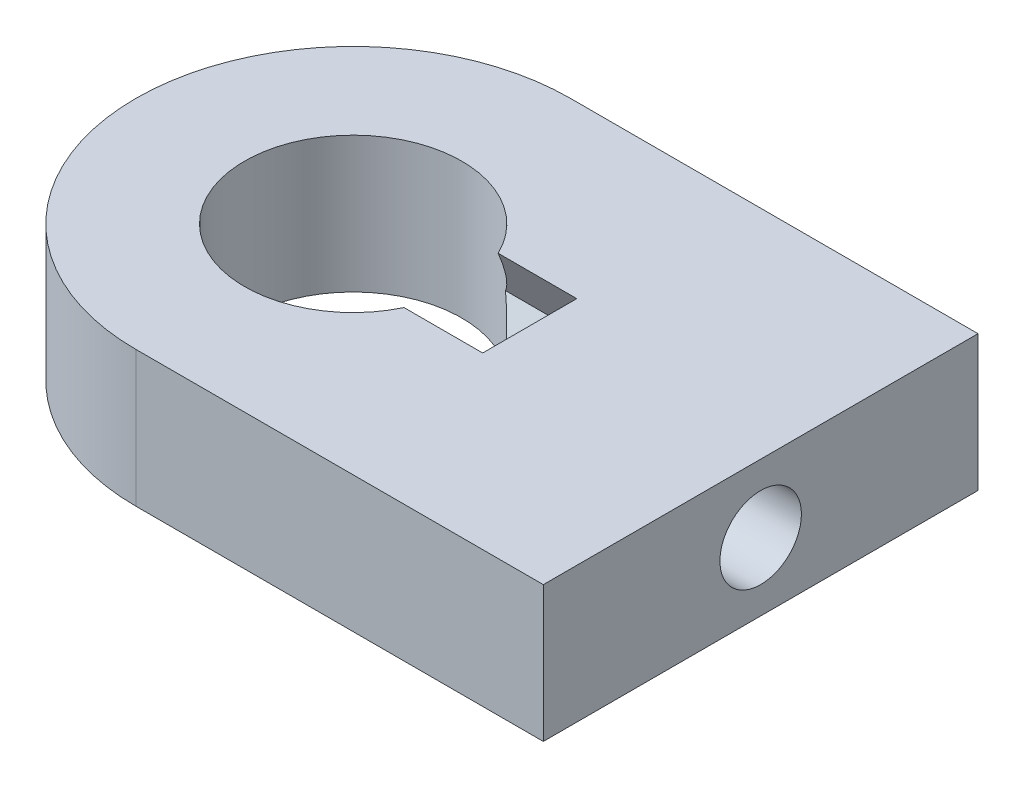
SolidWorks part; units mm, degrees
material "ABS"
ref_plane "Front Plane" through (0, 0, 0) normal (0, 0, 1) x (1, 0, 0)
ref_plane "Top Plane" through (0, 0, 0) normal (0, 1, 0) x (1, 0, 0)
ref_plane "Right Plane" through (0, 0, 0) normal (1, 0, 0) x (0, 0, -1)
sketch "Sketch1" plane through (0, 0, 0) normal (0, 1, 0) x (1, 0, 0)
  line L0 (0, 8) -> (15, 8)
  line L1 (15, 8) -> (15, -8)
  line L2 (15, -8) -> (0, -8)
  circle A0 centre (0, 0) radius 4
  arc A1 (0, -8) -> (0, 8) centre (0, 0) cw
  dimension "D1" = 8
  dimension "D2" = 8
  dimension "D3" = 15
extrude "Boss-Extrude1" add sketch "Sketch1" along normal blind 5
sketch "Sketch2" plane through (15, 0, 0) normal (1, 0, 0) x (0, 0, -1)
  line L0 (0, -3.0185) -> (0, 8.0813) construction
  line L1 (3.1754, 2.5) -> (1.5877, 5.25)
  line L2 (1.5877, 5.25) -> (-1.5877, 5.25)
  line L3 (-1.5877, 5.25) -> (-3.1754, 2.5)
  line L4 (-3.1754, 2.5) -> (-1.5877, -0.25)
  line L5 (-1.5877, -0.25) -> (1.5877, -0.25)
  line L6 (1.5877, -0.25) -> (3.1754, 2.5)
  line L7 (-8, 2.5) -> (8, 2.5) construction
  line L9 (-8, 5) -> (-8, 0) construction
  line L10 (8, 5) -> (8, 0) construction
  circle A0 centre (0, 2.5) radius 2.75 construction
  circle A1 centre (0, 2.5) radius 1.5
  dimension "D1" = 5.5
  dimension "D2" = 3
extrude "Cut-Extrude1" cut sketch "Sketch2" against normal up to next contours A1 region at (15, 2.5, 0)
sketch "Sketch3" plane through (0, 5, 0) normal (0, 1, 0) x (1, 0, 0)
  line L0 (6.5, 9.4882) -> (6.5, -10.0981) construction
  line L1 (0, -8) -> (15, -8) construction
  circle A0 centre (0, 0) radius 4 construction
  point P4 (6.5, -8)
  dimension "D1" = 6.5
extrude "Cut-Extrude2" cut sketch "Sketch2<4>" against normal up to next from vertex starting at point (6.5, 5, 8)
sketch "Sketch2<4>" plane through (15, 0, 0) normal (1, 0, 0) x (0, 0, -1) same geometry as "Sketch2"
equation "\"rod_diameter\"= 8"
equation "\"rod_hole_thickness\"= 4"
equation "\"rod_radius\"= \"rod_diameter\" / 2"
equation "\"platter_diameter\"= 320"
equation "\"platter_radius\"= \"platter_diameter\" / 2"
equation "\"extruder_mount_hole_spacing\"= 90"
equation "\"arm_rod_spacing\"= 40"
equation "\"top_frame_rod_spacing\"= \"arm_rod_spacing\" + 40"
equation "\"motor_level_rod_spacing\"= 15"
equation "\"linear_bearing_diameter\"= 15"
equation "\"z_rod_spacing\"= 75"
equation "\"platter_rod_spacing\"= 50"
equation "\"rod_nut_thickness\"= 6.5"
equation "\"rod_nut_inscribed_diameter\"= 13"
equation "\"z_height\"= 350"
equation "\"gear_pitch\"=2"
equation "\"r_gear_teeth\"= 450"
equation "\"theta_gear_teeth\"= 385"
equation "\"D1@Sketch1\"= \"rod_diameter\""
equation "\"D2@Sketch1\"=\"rod_radius\"+\"rod_hole_thickness\""
equation "\"D1@Sketch3\"=\"rod_radius\"+2.5"
